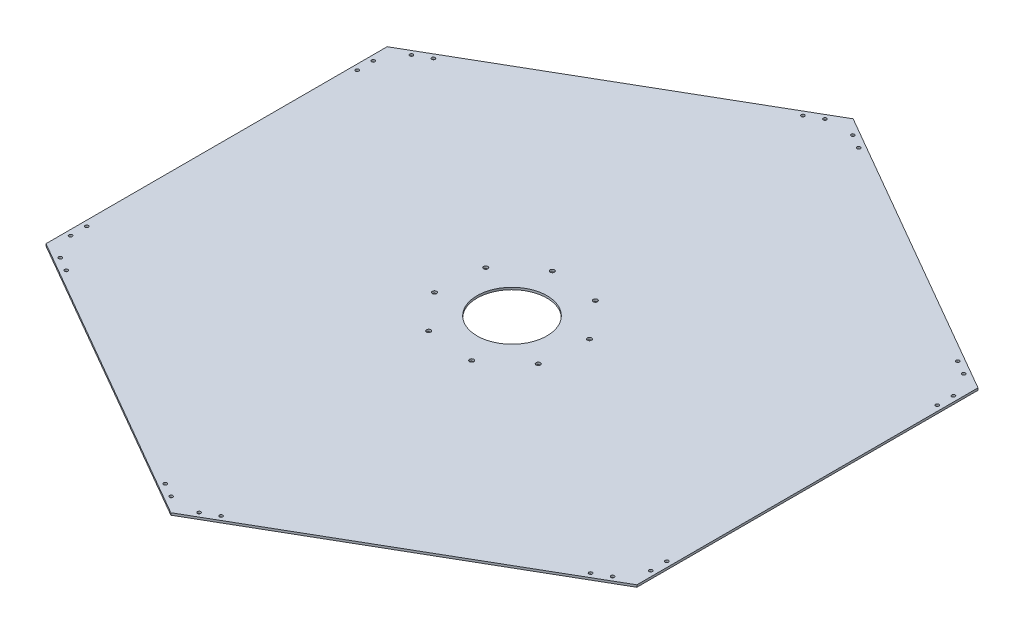
SolidWorks part; units mm, degrees
ref_plane "Front Plane" through (0, 0, 0) normal (0, 0, 1) x (1, 0, 0)
ref_plane "Top Plane" through (0, 0, 0) normal (0, 1, 0) x (1, 0, 0)
ref_plane "Right Plane" through (0, 0, 0) normal (1, 0, 0) x (0, 0, -1)
sketch "Sketch1" plane through (0, 0, 0) normal (0, 1, 0) x (1, 0, 0)
  line L0 (-1233.8651, 0) -> (1629.0875, 0) construction
  line L8 (0, 635.0853) -> (-550, 317.5426)
  line L9 (-550, 317.5426) -> (-550, -317.5426)
  line L10 (-550, -317.5426) -> (0, -635.0853)
  line L11 (0, -635.0853) -> (550, -317.5426)
  line L12 (550, -317.5426) -> (550, 317.5426)
  line L13 (550, 317.5426) -> (0, 635.0853)
  circle A0 centre (0, 0) radius 550 construction
  dimension "D1" = 1100
extrude "Boss-Extrude1" add sketch "Sketch1" along normal blind 4
sketch "Sketch3" plane through (0, 4, 0) normal (0, 1, 0) x (1, 0, 0)
  line L0 (0, -689.2362) -> (0, 663.4101) construction
  line L1 (0, 0) -> (53.1011, 102.0062) construction
  circle A0 centre (0, 0) radius 115 construction
  circle A1 centre (53.1011, 102.0062) radius 4
  circle A2 centre (109.6774, 34.5812) radius 4
  circle A3 centre (102.0062, -53.1011) radius 4
  circle A4 centre (34.5812, -109.6774) radius 4
  circle A5 centre (-53.1011, -102.0062) radius 4
  circle A6 centre (-109.6774, -34.5812) radius 4
  circle A7 centre (-102.0062, 53.1011) radius 4
  circle A8 centre (-34.5812, 109.6774) radius 4
  dimension "D1" = 230
  dimension "D3" = 8
  dimension "D2" = 27.5
  dimension "D4" = 8
extrude "Cut-Extrude1" cut sketch "Sketch3" against normal up to next
sketch "Sketch4" plane through (0, 4, 0) normal (0, 1, 0) x (1, 0, 0)
  line L0 (0, -978.554) -> (0, 843.7414) construction
  line L1 (550, 317.5426) -> (0, 635.0853) construction
  line L2 (550, 317.5426) -> (0, 635.0853) construction
  line L3 (0, 623.5383) -> (491.5063, 339.767) construction
  circle A0 centre (25.9808, 608.5383) radius 3.1
  circle A1 centre (51.9615, 593.5383) radius 3.1
  circle A2 centre (-51.9615, 593.5383) radius 3.1
  circle A3 centre (-25.9808, 608.5383) radius 3.1
  dimension "D4" = 6.2
  dimension "D1" = 10
  dimension "D2" = 30
  dimension "D3" = 30
extrude "Cut-Extrude2" cut sketch "Sketch4" against normal up to next
ref_axis "Axis1" through (0, 4.2, 0) along (0, -1, 0)
pattern_circular "CirPattern1" count 6 over 360 about axis through (0, 4.2, 0) along (0, -1, 0) of "Cut-Extrude2"
sketch "Sketch5" plane through (0, 4, 0) normal (0, 1, 0) x (1, 0, 0)
  circle A0 centre (0, 0) radius 65
  dimension "D1" = 130
extrude "Cut-Extrude3" cut sketch "Sketch5" against normal up to next
